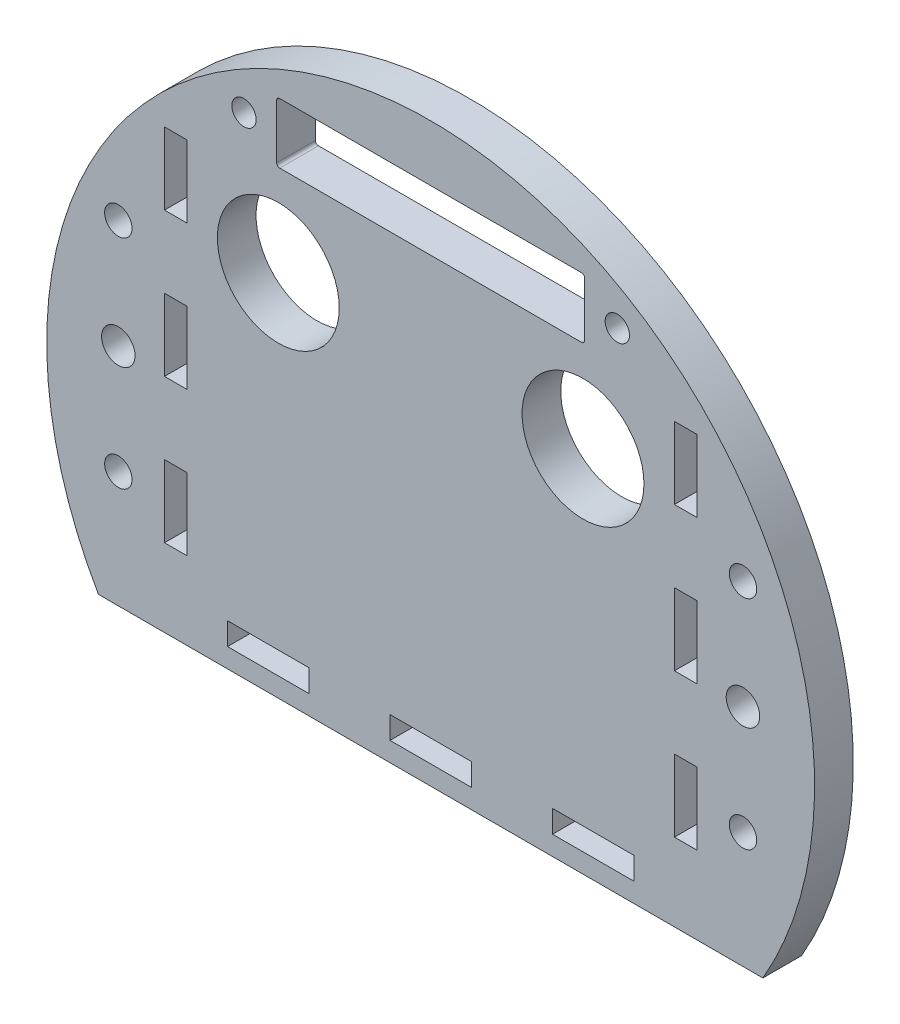
SolidWorks part; units mm, degrees
material "ABS"
ref_plane "Front Plane" through (0, 0, 0) normal (0, 0, 1) x (1, 0, 0)
ref_plane "Top Plane" through (0, 0, 0) normal (0, 1, 0) x (1, 0, 0)
ref_plane "Right Plane" through (0, 0, 0) normal (1, 0, 0) x (0, 0, -1)
sketch "Sketch1" plane through (0, 0, 0) normal (0, 0, 1) x (1, 0, 0)
  line L0 (0, 63) -> (0, -63) construction
  line L1 (-20, -28.4025) -> (-6.6667, -28.4025) construction
  line L2 (-40, -24.7275) -> (40, -24.7275) construction
  line L3 (-40, -24.7275) -> (-40, 40.2725) construction
  line L4 (-40, 40.2725) -> (40, 40.2725) construction
  line L5 (40, -24.7275) -> (40, 40.2725) construction
  line L6 (-40, -24.7275) -> (40, 40.2725) construction
  line L7 (-40, 40.2725) -> (40, -24.7275) construction
  line L8 (-24.765, 53.7686) -> (24.765, 53.7686)
  line L9 (-25.265, 53.2686) -> (-25.265, 44.3786)
  line L10 (-24.765, 43.8786) -> (24.765, 43.8786)
  line L11 (25.265, 53.2686) -> (25.265, 44.3786)
  line L12 (-25.265, 53.7686) -> (25.265, 43.8786) construction
  line L13 (-25.265, 43.8786) -> (25.265, 53.7686) construction
  line L14 (-37.5, -46.0775) -> (37.5, -46.0775) construction
  line L15 (-37.5, -46.0775) -> (-37.5, -31.5775) construction
  line L16 (-37.5, -31.5775) -> (37.5, -31.5775) construction
  line L17 (37.5, -46.0775) -> (37.5, -31.5775) construction
  line L18 (-37.5, -46.0775) -> (37.5, -31.5775) construction
  line L19 (-37.5, -31.5775) -> (37.5, -46.0775) construction
  line L32 (-33.3333, -24.7275) -> (-20, -24.7275)
  line L33 (-25.265, 53.7686) -> (-26.7923, 57.019) construction
  line L34 (-43.675, 28.4544) -> (-43.675, 16.6362) construction
  line L35 (-39.767, -48.863) -> (-37.5, -46.0775) construction
  line L36 (40, 40.2725) -> (43.675, 40.2725)
  line L37 (40, 40.2725) -> (40, 28.4544)
  line L38 (40, 28.4544) -> (43.675, 28.4544)
  line L39 (43.675, 40.2725) -> (43.675, 28.4544)
  line L40 (40, 16.6362) -> (43.675, 16.6362)
  line L41 (40, 16.6362) -> (40, 4.818)
  line L42 (40, 4.818) -> (43.675, 4.818)
  line L43 (43.675, 16.6362) -> (43.675, 4.818)
  line L44 (-40, 40.2725) -> (-43.675, 40.2725)
  line L45 (-40, 40.2725) -> (-40, 28.4544)
  line L46 (-40, 28.4544) -> (-43.675, 28.4544)
  line L47 (-43.675, 40.2725) -> (-43.675, 28.4544)
  line L48 (-40, 16.6362) -> (-43.675, 16.6362)
  line L49 (-40, 16.6362) -> (-40, 4.818)
  line L50 (-40, 4.818) -> (-43.675, 4.818)
  line L51 (-43.675, 16.6362) -> (-43.675, 4.818)
  line L52 (43.675, 28.4544) -> (43.675, 16.6362) construction
  line L53 (-43.675, 4.818) -> (-43.675, -7.0002) construction
  line L54 (-33.3333, -24.7275) -> (-33.3333, -28.4025)
  line L55 (43.675, 4.818) -> (43.675, -7.0002) construction
  line L56 (-43.675, -7.0002) -> (-40, -7.0002)
  line L57 (-43.675, 40.2725) -> (-46.3153, 42.7071) construction
  line L58 (-54.5148, -31.5775) -> (54.5148, -31.5775)
  line L59 (-30.6292, 48.8236) -> (30.6292, 48.8236) construction
  line L60 (-30.6292, 48.8236) -> (-33.4798, 53.3676) construction
  line L61 (-30.6292, 50.8236) -> (-25.265, 50.8236) construction
  line L62 (-43.675, -7.0002) -> (-43.675, -18.8184)
  line L63 (-43.675, -18.8184) -> (-40, -18.8184)
  line L64 (-40, -7.0002) -> (-40, -18.8184)
  line L65 (43.675, -7.0002) -> (40, -7.0002)
  line L66 (43.675, -7.0002) -> (43.675, -18.8184)
  line L67 (43.675, -18.8184) -> (40, -18.8184)
  line L68 (40, -7.0002) -> (40, -18.8184)
  line L69 (-33.3333, -28.4025) -> (-20, -28.4025)
  line L70 (-20, -24.7275) -> (-20, -28.4025)
  line L71 (-6.6667, -24.7275) -> (6.6667, -24.7275)
  line L72 (-6.6667, -24.7275) -> (-6.6667, -28.4025)
  line L73 (-6.6667, -28.4025) -> (6.6667, -28.4025)
  line L74 (6.6667, -24.7275) -> (6.6667, -28.4025)
  line L75 (20, -24.7275) -> (33.3333, -24.7275)
  line L76 (20, -24.7275) -> (20, -28.4025)
  line L77 (20, -28.4025) -> (33.3333, -28.4025)
  line L78 (33.3333, -24.7275) -> (33.3333, -28.4025)
  line L79 (6.6667, -28.4025) -> (20, -28.4025) construction
  line L80 (6.6667, -26.565) -> (13.3333, -26.565) construction
  line L81 (13.3333, -26.565) -> (20, -26.565) construction
  line L82 (-33.3333, -28.4025) -> (-40, -28.4025) construction
  line L83 (-40, -28.4025) -> (-40, -24.7275) construction
  line L84 (33.3333, -28.4025) -> (40, -28.4025) construction
  line L85 (40, -28.4025) -> (40, -24.7275) construction
  line L86 (-43.675, -18.8184) -> (-43.675, -24.7275) construction
  line L87 (-43.675, -24.7275) -> (-40, -24.7275) construction
  line L88 (43.675, -18.8184) -> (43.675, -24.7275) construction
  line L89 (43.675, -24.7275) -> (40, -24.7275) construction
  line L90 (-41.8375, 4.818) -> (-41.8375, -1.0911) construction
  line L91 (-41.8375, -1.0911) -> (-41.8375, -7.0002) construction
  line L92 (-40, 40.2725) -> (-40, 43.8786) construction
  line L93 (-40, 43.8786) -> (-25.265, 43.8786) construction
  line L94 (25.265, 43.8786) -> (40, 43.8786) construction
  line L95 (40, 43.8786) -> (40, 40.2725) construction
  line L96 (-40, 43.8786) -> (-25, 28.8786) construction
  line L97 (-25, 28.8786) -> (25, 28.8786) construction
  line L98 (25, 28.8786) -> (40, 43.8786) construction
  arc A1 (54.5148, -31.5775) -> (-54.5148, -31.5775) centre (0, 0) ccw
  circle A2 centre (51.25, 23.184) radius 2.25 construction
  circle A3 centre (51.25, -12.4964) radius 2.25 construction
  circle A4 centre (-51.25, -12.4964) radius 2.25 construction
  circle A5 centre (-51.25, 23.184) radius 2.25 construction
  circle A6 centre (51.25, 23.184) radius 2.25
  circle A7 centre (51.25, -12.4964) radius 2.25
  circle A8 centre (-51.25, -12.4964) radius 2.25
  circle A9 centre (-51.25, 23.184) radius 2.25
  arc A10 (60.1885, -18.6102) -> (-6.6055, -62.6528) centre (0, 0) ccw construction
  circle A11 centre (-51.25, 5.3438) radius 2.75
  circle A12 centre (51.25, 5.3438) radius 2.75
  arc A15 (-54.5148, -31.5775) -> (-39.767, -48.863) centre (0, 0) ccw construction
  arc A16 (-39.767, -48.863) -> (0, -63) centre (0, 0) ccw construction
  arc A17 (0, -63) -> (54.5148, -31.5775) centre (0, 0) ccw construction
  circle A18 centre (-30.6292, 48.8236) radius 2
  circle A19 centre (30.6292, 48.8236) radius 2
  arc A20 (24.765, 43.8786) -> (25.265, 44.3786) centre (24.765, 44.3786) ccw
  arc A21 (24.765, 53.7686) -> (25.265, 53.2686) centre (24.765, 53.2686) cw
  arc A22 (-25.265, 53.2686) -> (-24.765, 53.7686) centre (-24.765, 53.2686) cw
  arc A23 (-25.265, 44.3786) -> (-24.765, 43.8786) centre (-24.765, 44.3786) ccw
  circle A24 centre (-25, 28.8786) radius 10
  circle A25 centre (25, 28.8786) radius 10
  circle A26 centre (-25, 28.8786) radius 15 construction
  point P26 (0, 7.7725)
  point P31 (0, 48.8236)
  point P36 (0, -38.8275)
  dimension "D1" = 5.5
  dimension "D2" = 50.53
  dimension "D10" = 4
  dimension "D11" = 0.5
  dimension "D12" = 20
  dimension "D13" = 5
  dimension "D3" = 9.89
  dimension "D4" = 65
  dimension "D5" = 80
  dimension "D6" = 75
  dimension "D7" = 14.5
  dimension "D8" = 3.675
  dimension "D9" = 3.175
extrude "Boss-Extrude1" add sketch "Sketch1" along normal blind 6.35
